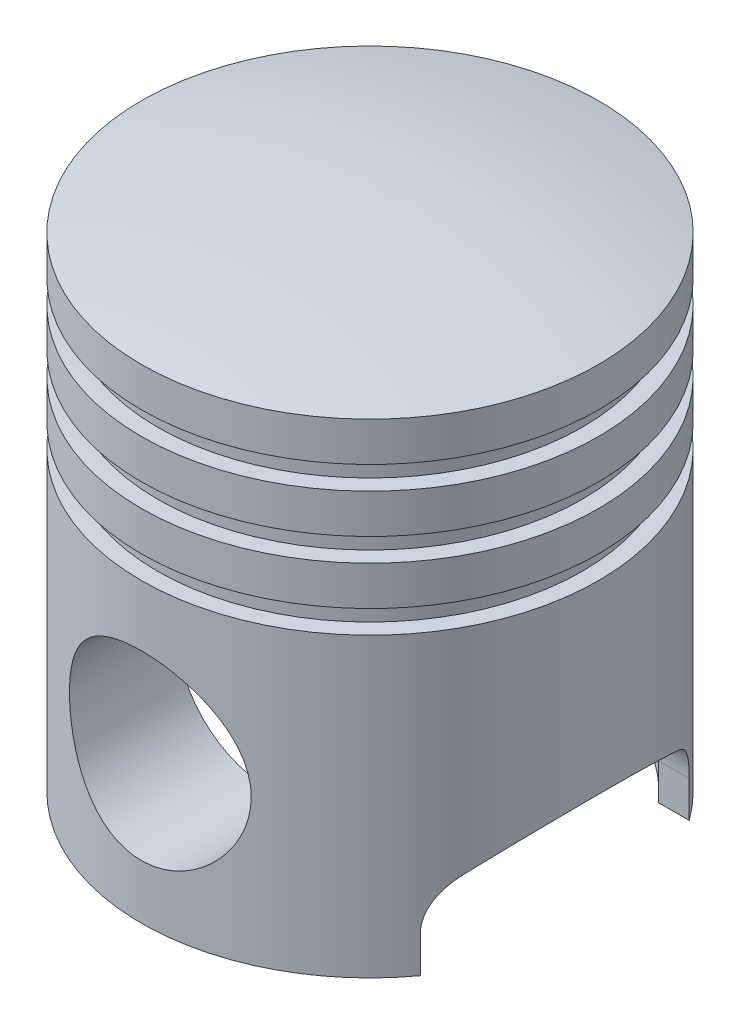
SolidWorks part; units mm, degrees
other "Sunlight"
ref_plane "Front Plane" through (0, 0, 0) normal (0, 0, 1) x (1, 0, 0)
ref_plane "Top Plane" through (0, 0, 0) normal (0, 1, 0) x (1, 0, 0)
ref_plane "Right Plane" through (0, 0, 0) normal (1, 0, 0) x (0, 0, -1)
sketch "Sketch6" plane through (0, 0, 0) normal (0, 1, 0) x (1, 0, 0)
  circle A0 centre (0, 0) radius 1079.5
  dimension "D1" = 2159
extrude "Boss-Extrude3" add sketch "Sketch6" along normal blind 2286
sketch "Sketch7" plane through (0, 2286, 0) normal (0, 1, 0) x (1, 0, 0)
  circle A0 centre (0, 0) radius 1003.3
  dimension "D1" = 2006.6
extrude "Cut-Extrude6" cut sketch "Sketch7" against normal blind 109.22 from offset 185.42 flip side to cut offset against normal yes
pattern_linear "LPattern1" count 3 spacing 294.64 along (0, -1, 0) of "Cut-Extrude6"
sketch "Sketch8" plane through (0, 0, 0) normal (0, -1, 0) x (1, 0, 0)
  circle A0 centre (0, 0) radius 965.2
  dimension "D1" = 1930.4
extrude "Cut-Extrude7" cut sketch "Sketch8" against normal blind 2159
dome "Dome1" faces to dome 1 distance 127 reverse direction no elliptical dome no face at (0, 2286, 1079.5) parameters "D1"=127
sketch "Sketch9" plane through (0, 0, 0) normal (0, 0, 1) x (1, 0, 0)
  circle A0 centre (0, 685.8) radius 429.26
  dimension "D1" = 858.52
  dimension "D2" = 685.8
extrude "Cut-Extrude9" cut sketch "Sketch9" against normal through all both and the other way through all contours A0
sketch "Sketch18" plane through (0, 0, 0) normal (1, 0, 0) x (0, 0, -1)
  line L0 (0, 0) -> (0, 769.9487) construction
  line L1 (-1079.5, 0) -> (1079.5, 0) construction
  line L2 (-635, 0) -> (-635, 304.8)
  line L3 (635, 0) -> (635, 304.8)
  line L4 (-635, 0) -> (635, 0)
  arc A0 (-635, 304.8) -> (635, 304.8) centre (0, -488.3147) cw
  dimension "D3" = 1016
  dimension "D1" = 304.8
  dimension "D2" = 1270
extrude "Cut-Extrude10" cut sketch "Sketch18" against normal through all both and the other way through all
fillet "Fillet1" radius 254 4 edges at (-799.9412, 304.8, -635) (-799.9412, 304.8, 635) (799.9412, 304.8, -635) (799.9412, 304.8, 635)
sketch "Sketch21" plane through (0, 0, 0) normal (0, 0, 1) x (1, 0, 0)
  circle A0 centre (0, 685.8) radius 429.26 construction
  circle A1 centre (0, 685.8) radius 429.26
  circle A2 centre (0, 685.8) radius 571.5
  dimension "D1" = 1143
extrude "Boss-Extrude8" add sketch "Sketch21" along normal up to next from offset 482.6
mirror "Mirror1" about plane through (0, 0, 0) normal (0, 0, 1) of "Boss-Extrude8"
